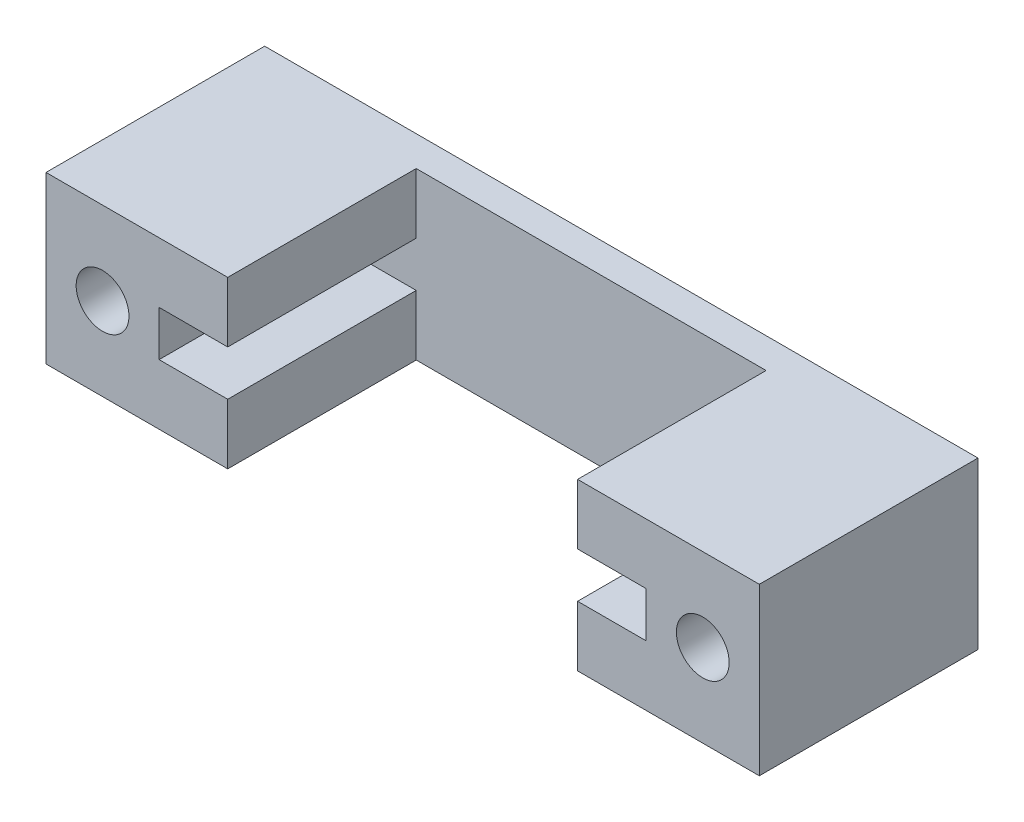
SolidWorks part; units mm, degrees
ref_plane "Front Plane" through (0, 0, 0) normal (0, 0, 1) x (1, 0, 0)
ref_plane "Top Plane" through (0, 0, 0) normal (0, 1, 0) x (1, 0, 0)
ref_plane "Right Plane" through (0, 0, 0) normal (1, 0, 0) x (0, 0, -1)
sketch "Sketch1" plane through (0, 0, 0) normal (0, 0, 1) x (1, 0, 0)
  line L18 (-11.6, 5.5) -> (11.6, 5.5)
  line L19 (11.6, 5.5) -> (11.6, 1.5)
  line L20 (11.6, 1.5) -> (16.15, 1.5)
  line L21 (16.15, 1.5) -> (16.15, -1.5)
  line L22 (16.15, -1.5) -> (11.6, -1.5)
  line L23 (11.6, -1.5) -> (11.6, -5.5)
  line L24 (11.6, -5.5) -> (-11.6, -5.5)
  line L25 (-11.6, -5.5) -> (-11.6, -1.5)
  line L26 (-11.6, -1.5) -> (-16.15, -1.5)
  line L27 (-16.15, -1.5) -> (-16.15, 1.5)
  line L28 (-16.15, 1.5) -> (-11.6, 1.5)
  line L29 (-11.6, 1.5) -> (-11.6, 5.5)
  line L30 (11.6, 5.5) -> (23.65, 5.5)
  line L31 (23.65, 5.5) -> (23.65, -5.5)
  line L32 (23.65, -5.5) -> (11.6, -5.5)
  line L33 (-11.6, 5.5) -> (-23.65, 5.5)
  line L34 (-23.65, 5.5) -> (-23.65, -5.5)
  line L35 (-23.65, -5.5) -> (-11.6, -5.5)
  line L36 (-16.15, 0) -> (-23.65, 0) construction
  line L37 (16.15, 0) -> (23.65, 0) construction
  circle A0 centre (-19.9, 0) radius 1.75
  circle A1 centre (19.9, 0) radius 1.75
  point P13 (16.15, 0)
  point P14 (0, 5.5)
  point P26 (-19.9, 0)
  point P29 (19.9, 0)
  dimension "D5" = 3.5
  dimension "D1" = 23.2
  dimension "D2" = 32.3
  dimension "D3" = 3
  dimension "D4" = 4
  dimension "D6" = 7.5
extrude "Boss-Extrude1" add sketch "Sketch1" along normal blind 2 contours L34 L35 L25 L26 L27 L28 L29 L33 A0 | L29 L28 L27 L26 L25 L24 L23 L22 L21 L20 L19 L18 | L32 L31 L30 L19 L20 L21 L22 L23 A1 region at (0, 0, 0) region at (-17.8931, 0, 0) region at (17.8931, 0, 0)
extrude "Boss-Extrude2" add sketch "Sketch1<3>" along normal blind 12.5 from surface contours L34 L35 L25 L26 L27 L28 L29 L33 A0 | L32 L31 L30 L19 L20 L21 L22 L23 A1 region at (-17.8931, 0, 0) region at (17.8931, 0, 0) starting at face at (0, 0, 2)
sketch "Sketch1<3>" plane through (0, 0, 0) normal (0, 0, 1) x (1, 0, 0) same geometry as "Sketch1"
